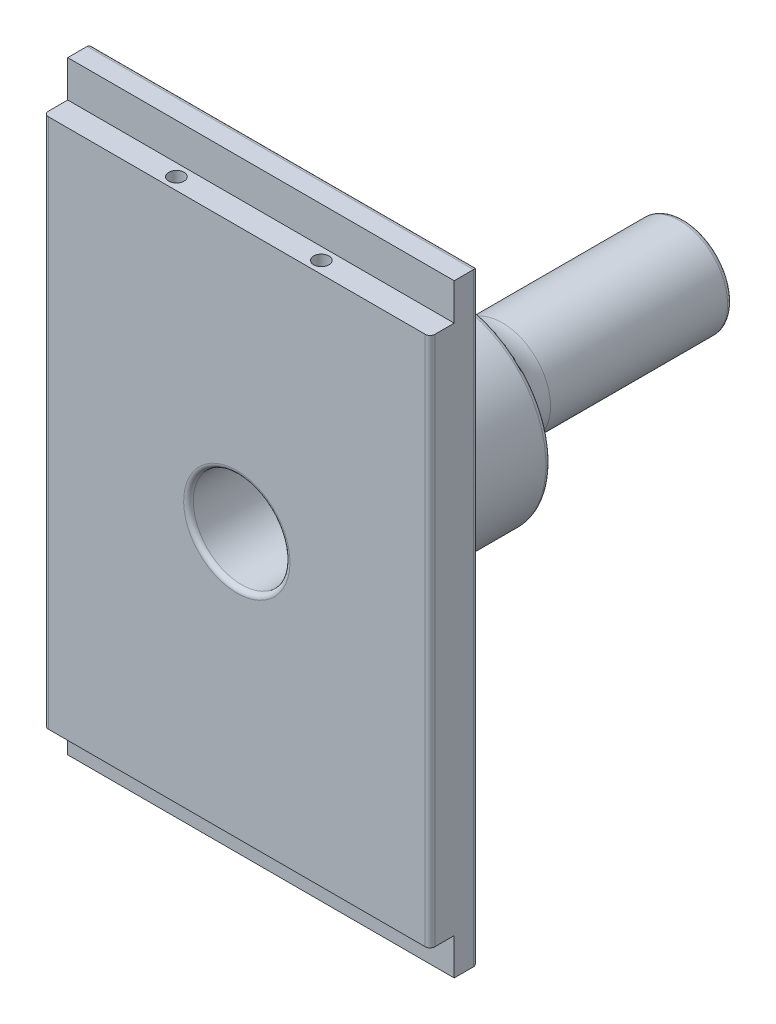
SolidWorks part; units mm, degrees
material "ABS"
ref_plane "Top Plane" through (0, 0, 0) normal (0, 0, 1) x (1, 0, 0)
ref_plane "Front Plane" through (0, 0, 0) normal (0, 1, 0) x (1, 0, 0)
ref_plane "Right Plane" through (0, 0, 0) normal (1, 0, 0) x (0, 0, -1)
sketch "Sketch1" plane through (0, 0, 0) normal (0, 1, 0) x (1, 0, 0)
  line L0 (0, 0) -> (0, -50.8) construction
  line L1 (0, -50.8) -> (-79.375, -50.8)
  line L2 (0, -50.8) -> (79.375, -50.8)
  line L3 (79.375, -50.8) -> (79.375, -57.15)
  line L4 (-79.375, -50.8) -> (-79.375, -57.15)
  line L5 (79.375, -57.15) -> (69.723, -57.15)
  line L6 (-79.375, -57.15) -> (-69.723, -57.15)
  line L7 (69.723, -57.15) -> (69.723, -63.5)
  line L8 (-69.723, -57.15) -> (-69.723, -63.5)
  line L9 (69.723, -63.5) -> (-69.723, -63.5)
  line L10 (36.4022, 0) -> (-31.9493, 0) construction
  dimension "D1" = 6.35
  dimension "D2" = 79.375
  dimension "D3" = 79.375
  dimension "D4" = 6.35
  dimension "D5" = 9.652
  dimension "D6" = 9.652
  dimension "D7" = 50.8
extrude "Boss-Extrude1" add sketch "Sketch1" along normal blind 50.8 and the other way blind 50.8
hole_wizard "#10-32 Tapped Hole1" positions "3DSketch1" profile "Sketch2" tap size "#10-32" standard "Ansi Inch"
sketch3d "3DSketch1"
  line L4 (-69.723, -50.8, 63.5) -> (-69.723, 50.8, 63.5) construction
  line L5 (-69.723, -50.8, 57.15) -> (-69.723, 50.8, 57.15) construction
  line L6 (-69.723, -19.05, 63.5) -> (-69.723, -19.05, 57.15) construction
  line L7 (-69.723, 50.8, 60.325) -> (-69.723, -50.8, 60.325) construction
  line L8 (-69.723, 50.8, 57.15) -> (-69.723, 50.8, 63.5) construction
  line L9 (-69.723, -50.8, 57.15) -> (-69.723, -50.8, 63.5) construction
  line L10 (-69.723, 19.05, 63.5) -> (-69.723, 19.05, 57.15) construction
  line L11 (69.723, -50.8, 60.325) -> (69.723, 50.8, 60.325) construction
  line L12 (69.723, -50.8, 63.5) -> (69.723, -50.8, 57.15) construction
  line L13 (69.723, 50.8, 63.5) -> (69.723, 50.8, 57.15) construction
  line L14 (69.723, -19.05, 63.5) -> (69.723, -19.05, 57.15) construction
  line L15 (69.723, -50.8, 63.5) -> (69.723, 50.8, 63.5) construction
  line L16 (69.723, -50.8, 57.15) -> (69.723, 50.8, 57.15) construction
  line L17 (69.723, 19.05, 63.5) -> (69.723, 19.05, 57.15) construction
  point P0 (-69.723, 19.05, 60.325)
  point P2 (-69.723, -19.05, 60.325)
  point P4 (69.723, 19.05, 60.325)
  point P6 (69.723, -19.05, 60.325)
  dimension "D1" = 31.75
  dimension "D2" = 31.75
  dimension "D3" = 31.75
  dimension "D4" = 31.75
sketch "Sketch2" plane through (-69.723, 19.05, 60.325) normal (0, 1, 0) x (0, 0, 1)
  line L0 (0, 0) -> (0, 26.6133)
  line L1 (0, 26.6133) -> (2.0193, 25.4)
  line L2 (2.0193, 25.4) -> (2.0193, 0)
  line L5 (2.0193, 0) -> (0, 0)
  line L10 (0, 26.6133) -> (-2.0193, 25.4) construction
  line L11 (0, -6.35) -> (0, 107.95) construction
  dimension "Tap Drill Dia." = 4.0386
  dimension "Tap Drill Depth" = 25.4
  dimension "Drill Angle" = 118
cosmetic thread "Hole Thread1" parameters "D1"=22.86, "D2"=4.826
cosmetic thread "Hole Thread2" parameters "D1"=22.86, "D2"=4.826
cosmetic thread "Hole Thread3" parameters "D1"=22.86, "D2"=4.826
cosmetic thread "Hole Thread4" parameters "D1"=22.86, "D2"=4.826
sketch "Sketch3" plane through (0, 0, 50.8) normal (0, 0, -1) x (-1, 0, 0)
  circle A0 centre (0, 0) radius 25.4
extrude "Boss-Extrude2" add sketch "Sketch3" along normal blind 44.45
sketch "Sketch4" plane through (0, 0, 6.35) normal (0, 0, -1) x (-1, 0, 0)
  circle A0 centre (0, 0) radius 12.7
extrude "Boss-Extrude3" add sketch "Sketch4" along normal blind 60.452
hole_wizard "1/4 (0.25) Diameter Hole1" positions "3DSketch2" profile "Sketch5" hole size "1/4" standard "Ansi Inch"
sketch3d "3DSketch2"
  point P0 (0, 0, 0)
  point P4 (0, 0, -54.102)
sketch "Sketch5" plane through (0, 0, -54.102) normal (1, 0, 0) x (0, 1, 0)
  line L0 (0, 0) -> (0, 27.3077)
  line L1 (0, 27.3077) -> (3.175, 25.4)
  line L2 (3.175, 25.4) -> (3.175, 0)
  line L5 (3.175, 0) -> (0, 0)
  line L10 (0, 27.3077) -> (-3.175, 25.4) construction
  line L11 (0, -6.35) -> (0, 107.95) construction
  dimension "Hole Dia." = 6.35
  dimension "Hole Depth" = 25.4
  dimension "Drill Angle" = 118
hole_wizard "1 (1) Diameter Hole1" positions "3DSketch3" profile "Sketch6" hole size "1" standard "Ansi Inch"
sketch3d "3DSketch3"
  point P0 (0, 0, 0)
  point P4 (0, 0, 63.5)
sketch "Sketch6" plane through (0, 0, 63.5) normal (1, 0, 0) x (0, -1, 0)
  line L0 (0, 0) -> (0, 58.4309)
  line L1 (0, 58.4309) -> (12.7, 50.8)
  line L2 (12.7, 50.8) -> (12.7, 0)
  line L5 (12.7, 0) -> (0, 0)
  line L10 (0, 58.4309) -> (-12.7, 50.8) construction
  line L11 (0, -6.35) -> (0, 107.95) construction
  dimension "Hole Dia." = 25.4
  dimension "Hole Depth" = 50.8
  dimension "Drill Angle" = 118
fillet "Fillet1" radius 1.27 10 edges at (-12.7, 0, -54.102) (-25.4, 0, 6.35) (-25.4, 0, 50.8) (12.7, 0, 63.5) (0, -50.8, 63.5) (0, -50.8, 50.8) (79.375, 0, 50.8) (-79.375, 0, 50.8) (0, 50.8, 50.8) (0, 50.8, 63.5)
fillet "Fillet2" radius 12.7 1 edges at (-12.7, 0, 6.35)
move or copy body "Body-Move/Copy1" bodies to move or copy 106 copy no rotation origin (0, 0, 0) rotation axis (0, 0, 1) rotation angle 90
